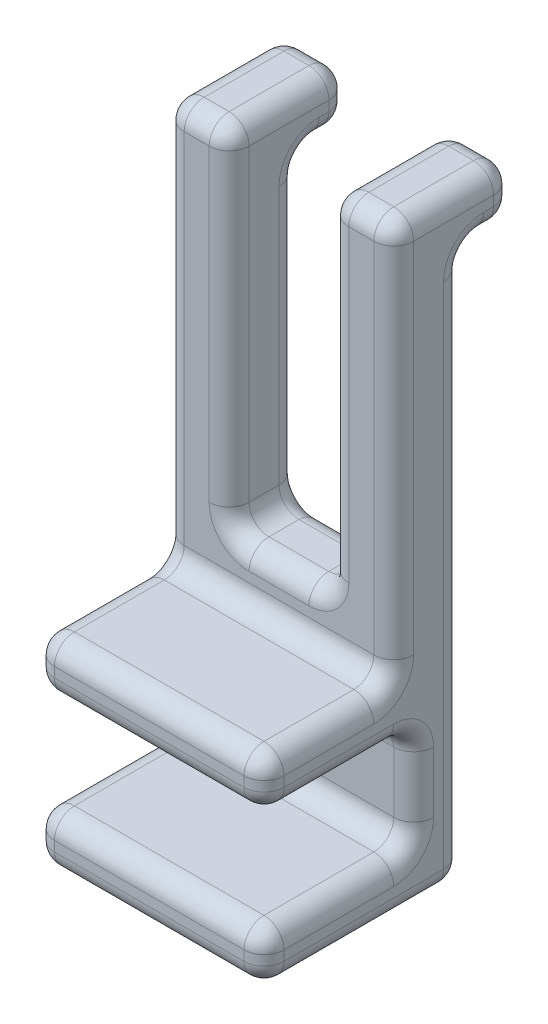
SolidWorks part; units mm, degrees
ref_plane "Front Plane" through (0, 0, 0) normal (0, 0, 1) x (1, 0, 0)
ref_plane "Top Plane" through (0, 0, 0) normal (0, 1, 0) x (1, 0, 0)
ref_plane "Right Plane" through (0, 0, 0) normal (1, 0, 0) x (0, 0, -1)
sketch "Sketch1" plane through (0, 0, 0) normal (0, 0, 1) x (1, 0, 0)
  line L1 (0, 0) -> (-23, 0)
  line L2 (0, 0) -> (0, 60)
  line L3 (0, 60) -> (-23, 60)
  line L4 (-23, 0) -> (-23, 60)
  dimension "D1" = 60
  dimension "D2" = 23
extrude "Boss-Extrude1" add sketch "Sketch1" along normal blind 20
sketch "Sketch2" plane through (0, 0, 0) normal (1, 0, 0) x (0, 0, -1)
  line L0 (-20, 0) -> (-20, 60) construction
  line L1 (-20, 15.1) -> (-5, 15.1)
  line L2 (-20, 15.1) -> (-20, 5)
  line L3 (-20, 5) -> (-5, 5)
  line L4 (-5, 15.1) -> (-5, 5)
  line L5 (-20, 0) -> (0, 0) construction
  line L6 (0, 0) -> (0, 60) construction
  dimension "D1" = 5
  dimension "D2" = 5
  dimension "10,5" = 10.1
extrude "Cut-Extrude1" cut sketch "Sketch2" against normal through all
fillet "Fillet1" radius 2 8 edges at (-23, 5, 12.5) (0, 5, 12.5) (-23, 15.1, 12.5) (0, 15.1, 12.5) (-11.5, 5, 5) (-23, 10.05, 5) (-11.5, 15.1, 5) (0, 10.05, 5)
sketch "Sketch4" plane through (-23, 0, 0) normal (-1, 0, 0) x (0, 0, 1)
  line L1 (20, 20.1) -> (7, 20.1)
  line L2 (20, 20.1) -> (20, 60)
  line L3 (20, 60) -> (7, 60)
  line L4 (7, 20.1) -> (7, 60)
  line L12 (20, 15.1) -> (7, 15.1) construction
  dimension "D1" = 5
extrude "Cut-Extrude3" cut sketch "Sketch4" against normal through all
sketch "Sketch6" plane through (0, 0, 0) normal (0, 0, -1) x (-1, 0, 0)
  line L1 (0, 60) -> (23, 60)
  line L2 (0, 60) -> (0, 55)
  line L3 (0, 55) -> (23, 55)
  line L4 (23, 60) -> (23, 55)
  dimension "D1" = 5
extrude "Boss-Extrude2" add sketch "Sketch6" along normal blind 5
sketch "Sketch5" plane through (0, 0, 0) normal (0, 0, -1) x (-1, 0, 0)
  line L0 (23, 55) -> (23, 0) construction
  line L1 (6.5, 60) -> (16.5, 60)
  line L2 (6.5, 60) -> (6.5, 25.1)
  line L3 (6.5, 25.1) -> (16.5, 25.1)
  line L4 (16.5, 60) -> (16.5, 25.1)
  line L5 (0, 0) -> (0, 55) construction
  line L6 (6.5, 25.1) -> (16.5, 25.1) construction
  line L7 (23, 60) -> (0, 60) construction
  line L8 (0, 55) -> (23, 55) construction
  line L9 (0, 55) -> (23, 55) construction
  line L11 (0, 20.1) -> (23, 20.1) construction
  point P16 (11.5, 25.1)
  point P17 (11.5, 55)
  dimension "D1" = 10
  dimension "D2" = 5
extrude "Cut-Extrude4" cut sketch "Sketch5" against normal up to next and the other way through all
fillet "Fillet11" radius 2 50 edges at (-6.5, 25.1, 3.5) (-16.5, 25.1, 3.5) (-16.5, 60, 1) (-6.5, 60, 1) (-0.5858, 4.4142, 20) (-22.4142, 4.4142, 20) (-0.5858, 15.6858, 20) (-22.4142, 15.6858, 20) (-11.5, 20.1, 20) (-3.25, 60, 7) (-11.5, 20.1, 7) (-19.75, 60, 7) (-16.5, 42.55, 7) (-11.5, 25.1, 7) (-6.5, 42.55, 7) (0, 60, 1) (0, 1.5, 20) (0, 18.6, 20) (0, 20.1, 13.5) (0, 40.05, 7) (-11.5, 15.1, 20) (-11.5, 5, 20) (-11.5, 0, 20) (0, 0, 10) (-23, 1.5, 20) (-23, 0, 10) (-23, 60, 1) (-23, 40.05, 7) (-23, 20.1, 13.5) (-23, 18.6, 20) (-23, 57.5, -5) (-16.5, 57.5, -5) (-19.75, 60, -5) (-19.75, 55, -5) (-23, 55, -2.5) (-16.5, 55, -2.5) (0, 55, -2.5) (-6.5, 55, -2.5) (0, 57.5, -5) (-3.25, 60, -5) (-6.5, 57.5, -5) (-3.25, 55, -5) (-11.5, 25.1, 0) (-16.5, 40.05, 0) (-19.75, 55, 0) (-23, 27.5, 0) (-11.5, 0, 0) (0, 27.5, 0) (-3.25, 55, 0) (-6.5, 40.05, 0)
